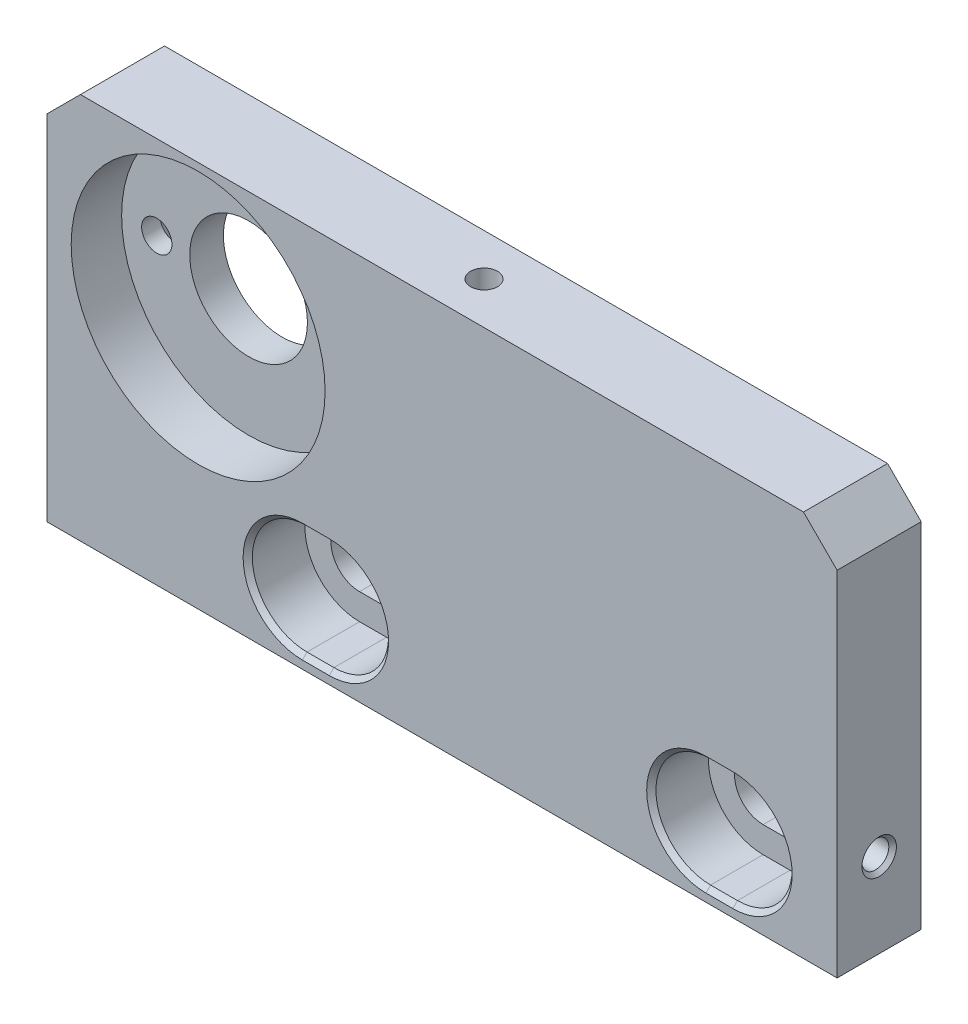
SolidWorks part; units mm, degrees
material "3.3547 (EN-AW 5083)"
ref_plane "Vorne" through (0, 0, 0) normal (0, 0, 1) x (1, 0, 0)
ref_plane "Oben" through (0, 0, 0) normal (0, 1, 0) x (1, 0, 0)
ref_plane "Rechts" through (0, 0, 0) normal (1, 0, 0) x (0, 0, -1)
sketch "Skizze1" plane through (0, 0, 0) normal (0, 0, 1) x (1, 0, 0)
  line L1 (-23.5, -11.5) -> (23.5, -11.5)
  line L2 (-23.5, -11.5) -> (-23.5, 11.5)
  line L3 (-23.5, 11.5) -> (23.5, 11.5)
  line L4 (23.5, -11.5) -> (23.5, 11.5)
  line L5 (-23.5, -11.5) -> (23.5, 11.5) construction
  line L6 (-23.5, 11.5) -> (23.5, -11.5) construction
  point P0 (0, 0)
  dimension "D1" = 47
  dimension "D2" = 23
extrude "Aufsatz-Linear austragen1" add sketch "Skizze1" along normal blind 5
sketch "Skizze2" plane through (0, 0, 5) normal (0, 0, 1) x (1, 0, 0)
  line L0 (23.5, 11.5) -> (-23.5, 11.5) construction
  line L1 (-23.5, 11.5) -> (-23.5, -11.5) construction
  circle A0 centre (-14.5, 3.5) radius 7.55
  dimension "D1" = 15.1
  dimension "D2" = 8
  dimension "D3" = 9
extrude "Schnitt-Linear austragen1" cut sketch "Skizze2" against normal blind 3
sketch "Skizze3" plane through (0, 0, 5) normal (0, 0, 1) x (1, 0, 0)
  circle A0 centre (-14.5, 3.5) radius 3.5
  dimension "D1" = 7
extrude "Schnitt-Linear austragen2" cut sketch "Skizze3" against normal through all
hole_wizard "Formsenkung für M1.6 Senkschraube mit Schlitz/Kreuzschlitz1" positions "Skizze8" profile "Skizze9" countersink size "M1.6" standard "DIN" end condition through all
sketch "Skizze8" plane through (0, 0, 0) normal (0, 0, -1) x (-1, 0, 0)
  line L0 (14.5, 3.5) -> (19.96, 3.5) construction
  point P1 (19.96, 3.5)
  point P7 (9.04, 3.5)
  dimension "D1" = 5.46
  dimension "D2" = 10.92
sketch "Skizze9" plane through (-9.04, 3.5, 0) normal (1, 0, 0) x (0, 1, 0)
  line L0 (0, 0) -> (0, 5)
  line L1 (0, 5) -> (0.9, 5)
  line L2 (0.9, 5) -> (0.9, 0.9)
  line L3 (0.9, 0.9) -> (1.8, 0)
  line L5 (1.8, 0) -> (0, 0)
  line L6 (-0.9, 0.9) -> (-1.8, 0) construction
  line L11 (0, -6.35) -> (0, 107.95) construction
  dimension "Bohrerdurchmesser" = 1.8
  dimension "Bohrungstiefe" = 5
  dimension "Senkdurchmesser (Oben)" = 3.6
  dimension "Senkwinkel (Oben)" = 90
hole_wizard "M2 Gewindebohrung1" positions "Skizze12" profile "Skizze13" tap size "M2" standard "DIN"
sketch "Skizze12" plane through (-23.5, 0, 0) normal (-1, 0, 0) x (0, 0, 1)
  line L0 (5, -11.5) -> (0, -11.5) construction
  line L1 (0, -12.65) -> (0, 12.65) construction
  point P0 (2.5, -6.5)
  dimension "D1" = 5
  dimension "D2" = 2.5
sketch "Skizze13" plane through (-23.5, -6.5, 2.5) normal (0, 1, 0) x (0, 0, 1)
  line L0 (0, 0) -> (0, 8.4807)
  line L1 (0, 8.4807) -> (0.8, 8)
  line L2 (0.8, 8) -> (0.8, 0.225)
  line L3 (0.8, 0.225) -> (1.025, 0)
  line L5 (1.025, 0) -> (0, 0)
  line L6 (-0.8, 0.225) -> (-1.025, 0) construction
  line L10 (0, 8.4807) -> (-0.8, 8) construction
  line L11 (0, -6.35) -> (0, 107.95) construction
  dimension "Bohrerdurchmesser" = 1.6
  dimension "Bohrungstiefe" = 8
  dimension "Senkdurchmesser (Oben)" = 2.05
  dimension "Senkwinkel (Oben)" = 90
  dimension "Spitzenwinkel" = 118
cosmetic thread "Bohrungsgewinde1"
hole_wizard "M2 Gewindebohrung2" positions "Skizze14" profile "Skizze15" tap size "M2" standard "DIN"
sketch "Skizze14" plane through (23.5, 0, 0) normal (1, 0, 0) x (0, 0, -1)
  line L0 (-5, -11.5) -> (0, -11.5) construction
  line L1 (0, 12.65) -> (0, -12.65) construction
  point P0 (-2.5, -6.5)
  dimension "D1" = 5
  dimension "D2" = 2.5
sketch "Skizze15" plane through (23.5, -6.5, 2.5) normal (0, 1, 0) x (0, 0, -1)
  line L0 (0, 0) -> (0, 8.4807)
  line L1 (0, 8.4807) -> (0.8, 8)
  line L2 (0.8, 8) -> (0.8, 0.225)
  line L3 (0.8, 0.225) -> (1.025, 0)
  line L5 (1.025, 0) -> (0, 0)
  line L6 (-0.8, 0.225) -> (-1.025, 0) construction
  line L10 (0, 8.4807) -> (-0.8, 8) construction
  line L11 (0, -6.35) -> (0, 107.95) construction
  dimension "Bohrerdurchmesser" = 1.6
  dimension "Bohrungstiefe" = 8
  dimension "Senkdurchmesser (Oben)" = 2.05
  dimension "Senkwinkel (Oben)" = 90
  dimension "Spitzenwinkel" = 118
cosmetic thread "Bohrungsgewinde2"
hole_wizard "M2 Gewindebohrung3" positions "Skizze16" profile "Skizze17" tap size "M2" standard "DIN"
sketch "Skizze16" plane through (0, 11.5, 0) normal (0, 1, 0) x (1, 0, 0)
  line L0 (-23.5, -5) -> (-23.5, 0) construction
  line L1 (23.5, 0) -> (-23.5, 0) construction
  point P0 (0, -2.5)
  dimension "D1" = 23.5
  dimension "D2" = 2.5
sketch "Skizze17" plane through (0, 11.5, 2.5) normal (1, 0, 0) x (0, 0, 1)
  line L0 (0, 0) -> (0, 8.4807)
  line L1 (0, 8.4807) -> (0.8, 8)
  line L2 (0.8, 8) -> (0.8, 0)
  line L5 (0.8, 0) -> (0, 0)
  line L10 (0, 8.4807) -> (-0.8, 8) construction
  line L11 (0, -6.35) -> (0, 107.95) construction
  dimension "Bohrerdurchmesser" = 1.6
  dimension "Bohrungstiefe" = 8
  dimension "Spitzenwinkel" = 118
cosmetic thread "Bohrungsgewinde3" parameters "D1"=6, "D2"=2
chamfer "Fase1" distance 2 angle 45 2 edges at (23.5, 11.5, 2.5) (-23.5, 11.5, 2.5)
hole_wizard "Stirnsenkung Langloch für M3 Zylinderschraube mit Innensechskant2" positions "Skizze18" profile "Skizze19" size "M3" standard "DIN" slot yes end condition through all
sketch "Skizze18" plane through (0, 0, 5) normal (0, 0, 1) x (1, 0, 0)
  line L0 (14, -7.5) -> (19, -7.5) construction
  line L1 (-23.5, -11.5) -> (23.5, -11.5) construction
  line L2 (23.5, -11.5) -> (23.5, 9.5) construction
  point P0 (16.5, -7.5)
  point P4 (-7.5, -7.5)
  dimension "D1" = 5
  dimension "D2" = 4
  dimension "D3" = 7
  dimension "D4" = 31
sketch "Skizze19" plane through (16.5, -7.5, 5) normal (1, 0, 0) x (0, -1, 0)
  line L0 (0, 0) -> (0, 5)
  line L1 (0, 5) -> (1.7, 5)
  line L3 (1.7, 5) -> (1.7, 3.4)
  line L4 (3.25, 3.4) -> (1.7, 3.4)
  line L5 (3.25, 3.4) -> (3.25, 0.275)
  line L6 (3.25, 0.275) -> (3.525, 0)
  line L7 (3.525, 0) -> (0, 0)
  line L8 (-3.25, 0.275) -> (-3.525, 0) construction
  line L11 (0, -6.35) -> (0, 107.95) construction
  dimension "Bohrerdurchmesser" = 3.4
  dimension "Bohrungstiefe" = 5
  dimension "Senkdurchmesser2" = 6.5
  dimension "Senktiefe2" = 3.4
  dimension "Senkdurchmesser4 (Oben)" = 7.05
  dimension "Senkwinkel2 (Oben)" = 90
